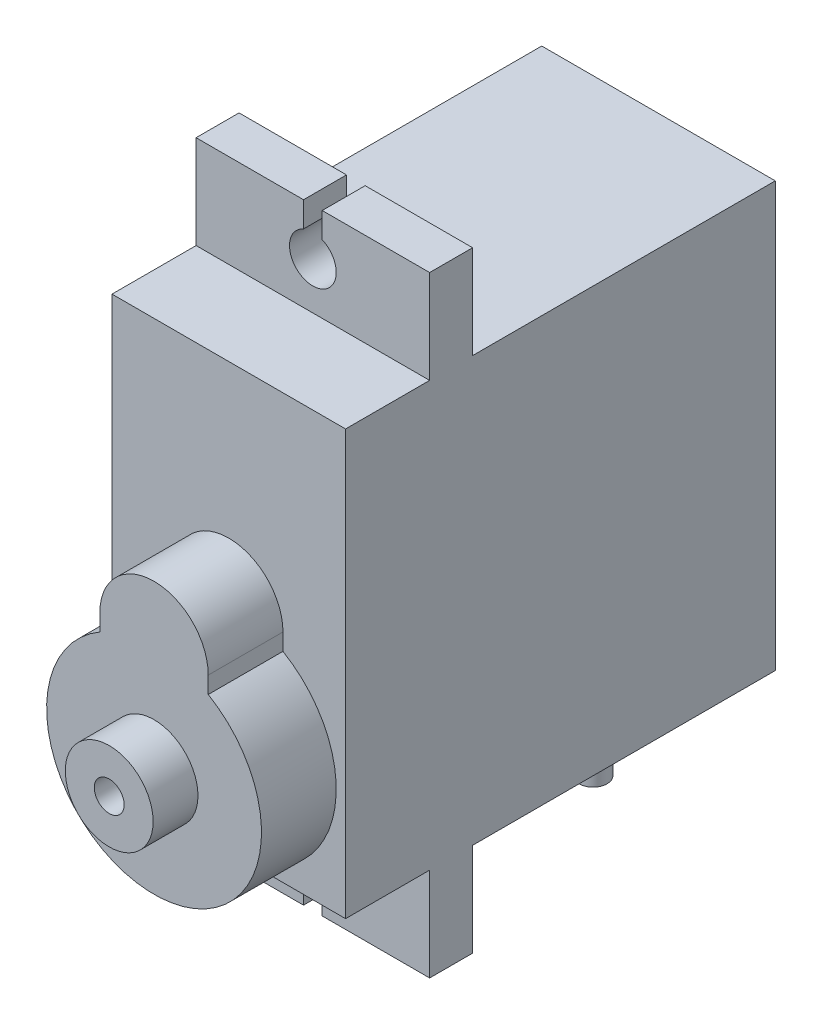
SolidWorks part; units mm, degrees
ref_plane "Alzado" through (0, 0, 0) normal (0, 0, 1) x (1, 0, 0)
ref_plane "Planta" through (0, 0, 0) normal (0, 1, 0) x (1, 0, 0)
ref_plane "Vista lateral" through (0, 0, 0) normal (1, 0, 0) x (0, 0, -1)
sketch "Sketch1" plane through (0, 0, 0) normal (0, 0, 1) x (1, 0, 0)
  line L1 (-6.25, -11.35) -> (6.25, -11.35)
  line L2 (-6.25, -11.35) -> (-6.25, 11.35)
  line L3 (-6.25, 11.35) -> (6.25, 11.35)
  line L4 (6.25, -11.35) -> (6.25, 11.35)
  line L5 (-6.25, -11.35) -> (6.25, 11.35) construction
  line L6 (-6.25, 11.35) -> (6.25, -11.35) construction
  point P0 (0, 0)
  dimension "D1" = 22.7
  dimension "D2" = 12.5
extrude "Boss-Extrude1" add sketch "Sketch1" along normal blind 23
sketch "Sketch2" plane through (0, 0, 23) normal (0, 0, 1) x (1, 0, 0)
  line L0 (-6.25, -11.35) -> (6.25, -11.35) construction
  line L1 (2.9, 0.2651) -> (2.9, -0.6349)
  line L2 (-2.9, 0.2651) -> (-2.9, -0.6349)
  line L3 (0, 0) -> (0, 11.35) construction
  line L4 (6.25, 11.35) -> (-6.25, 11.35) construction
  arc A0 (-2.9, -0.6349) -> (2.9, -0.6349) centre (0, -5.6) ccw
  arc A1 (2.9, 0.2651) -> (-2.9, 0.2651) centre (0, 0.2651) ccw
  dimension "D1" = 11.5
  dimension "D2" = 5.8
  dimension "D3" = 0.9
extrude "Boss-Extrude2" add sketch "Sketch2" along normal blind 4
sketch "Sketch3" plane through (0, 0, 0) normal (1, 0, 0) x (0, 0, -1)
  line L0 (-23, 11.35) -> (0, 11.35) construction
  line L1 (-16.2, 11.35) -> (-18.5, 11.35)
  line L2 (-16.2, 11.35) -> (-16.2, 16.35)
  line L3 (-16.2, 16.35) -> (-18.5, 16.35)
  line L4 (-18.5, 11.35) -> (-18.5, 16.35)
  line L5 (-23, -11.35) -> (-23, 11.35) construction
  line L6 (0, 0) -> (-23, 0) construction
  line L7 (-18.5, -11.35) -> (-18.5, -16.35)
  line L8 (-16.2, -11.35) -> (-16.2, -16.35)
  line L9 (-16.2, -11.35) -> (-18.5, -11.35)
  line L10 (-16.2, -16.35) -> (-18.5, -16.35)
  dimension "D1" = 4.5
  dimension "D2" = 2.3
  dimension "D3" = 5
extrude "Boss-Extrude3" add sketch "Sketch3" along normal mid plane 12.5
sketch "Sketch4" plane through (0, 0, 18.5) normal (0, 0, 1) x (1, 0, 0)
  line L0 (0, 16.35) -> (0, 11.35) construction
  line L1 (6.25, 16.35) -> (-6.25, 16.35) construction
  line L2 (6.25, 11.35) -> (-6.25, 11.35) construction
  line L3 (-6.25, 0) -> (6.25, 0) construction
  line L4 (-6.25, 11.35) -> (-6.25, -11.35) construction
  line L5 (6.25, -11.35) -> (6.25, 11.35) construction
  line L6 (0.5, -15.6728) -> (-0.5, -15.6728) construction
  line L7 (0.5, 16.35) -> (-0.5, 16.35)
  line L8 (0.5, 16.35) -> (0.5, 14.9956)
  line L9 (0, -14.9956) -> (0, -16.35) construction
  line L10 (-0.5, 16.35) -> (-0.5, 14.9956)
  line L11 (0, 14.9956) -> (0, 16.35) construction
  line L12 (0.5, 15.6728) -> (-0.5, 15.6728) construction
  line L13 (0, -16.35) -> (0, -11.35) construction
  line L14 (-0.5, -16.35) -> (-0.5, -14.9956)
  line L15 (0.5, -16.35) -> (0.5, -14.9956)
  line L16 (0.5, -16.35) -> (-0.5, -16.35)
  arc A0 (-0.5, 14.9956) -> (0.5, 14.9956) centre (0, 13.85) ccw
  arc A1 (-0.5, -14.9956) -> (0.5, -14.9956) centre (0, -13.85) cw
  point P27 (0, -15.6728)
  point P124 (0, 15.6728)
  dimension "D1" = 2.5
  dimension "D2" = 1
extrude "Cut-Extrude1" cut sketch "Sketch4" against normal up to next
sketch "Sketch5" plane through (0, 0, 0) normal (0, 0, -1) x (-1, 0, 0)
  line L0 (-6.25, -11.35) -> (6.25, -11.35) construction
  line L1 (-2, -11.35) -> (2, -11.35)
  line L2 (-2, -11.35) -> (-2, -16.35)
  line L3 (-2, -16.35) -> (2, -16.35)
  line L4 (2, -11.35) -> (2, -16.35)
  line L5 (0, -11.35) -> (0, 0) construction
  line L6 (-6.25, -16.35) -> (-0.5, -16.35) construction
  dimension "D1" = 4
extrude "Boss-Extrude4" add sketch "Sketch5" against normal blind 1.5 from offset 4 offset against normal yes
sketch "Sketch6" plane through (0, 0, 27) normal (0, 0, 1) x (1, 0, 0)
  circle A0 centre (0, -5.6) radius 2.35
  circle A1 centre (0, -5.6) radius 0.8
  dimension "D1" = 4.7
  dimension "D2" = 1.6
extrude "Boss-Extrude5" add sketch "Sketch6" along normal blind 2.4
sketch "Sketch7" plane through (0, -16.35, 0) normal (0, -1, 0) x (1, 0, 0)
  line L0 (2, 5.5) -> (-2, 5.5) construction
  line L1 (-2, 4) -> (2, 4) construction
  line L2 (2, 5.5) -> (2, 4) construction
  line L3 (0, 5.5) -> (0, 0) construction
  line L4 (-2, 5.5) -> (2, 5.5) construction
  line L6 (-2.2574, 3.6981) -> (2.2574, 3.6981)
  line L7 (-2.2574, 3.6981) -> (-2.2574, 5.8019)
  line L8 (-2.2574, 5.8019) -> (2.2574, 5.8019)
  line L9 (2.2574, 3.6981) -> (2.2574, 5.8019)
  line L10 (-2.2574, 3.6981) -> (2.2574, 5.8019) construction
  line L11 (-2.2574, 5.8019) -> (2.2574, 3.6981) construction
  arc A0 (-0.625, 4.3354) -> (-0.625, 5.1646) centre (-1.25, 4.75) cw
  arc A1 (-0.625, 4.3354) -> (0.625, 4.3354) centre (0, 4.75) ccw
  arc A2 (0.625, 4.3354) -> (0.625, 5.1646) centre (1.25, 4.75) ccw
  arc A3 (0.625, 5.1646) -> (-0.625, 5.1646) centre (0, 4.75) ccw
extrude "Cut-Extrude2" cut sketch "Sketch7" against normal up to surface (5 mm away) up to face at (0, -11.35, 8.1)
